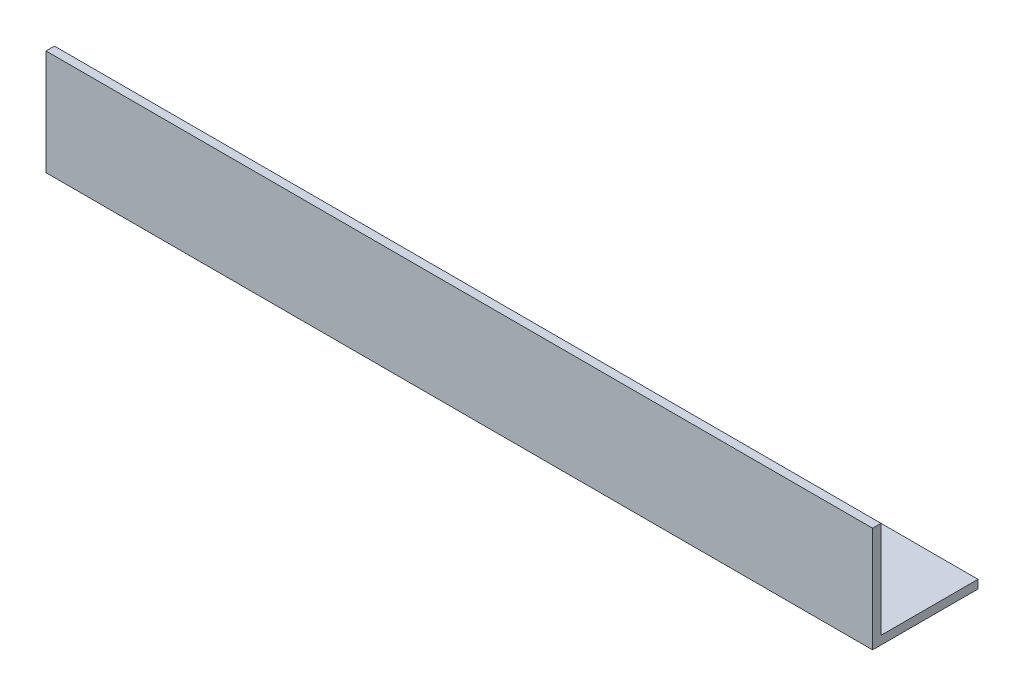
SolidWorks part; units mm, degrees
ref_plane "Спереди" through (0, 0, 0) normal (0, 0, 1) x (1, 0, 0)
ref_plane "Сверху" through (0, 0, 0) normal (0, 1, 0) x (1, 0, 0)
ref_plane "Справа" through (0, 0, 0) normal (1, 0, 0) x (0, 0, -1)
sketch "Эскиз1" plane through (0, 0, 0) normal (1, 0, 0) x (0, 0, -1)
  line L0 (0, 25) -> (0, 0)
  line L1 (0, 0) -> (25, 0)
extrude "Вытянуть-Тонкостенный1" add sketch "Эскиз1" along normal blind 196 thin thin type one direction reverse wall 2
